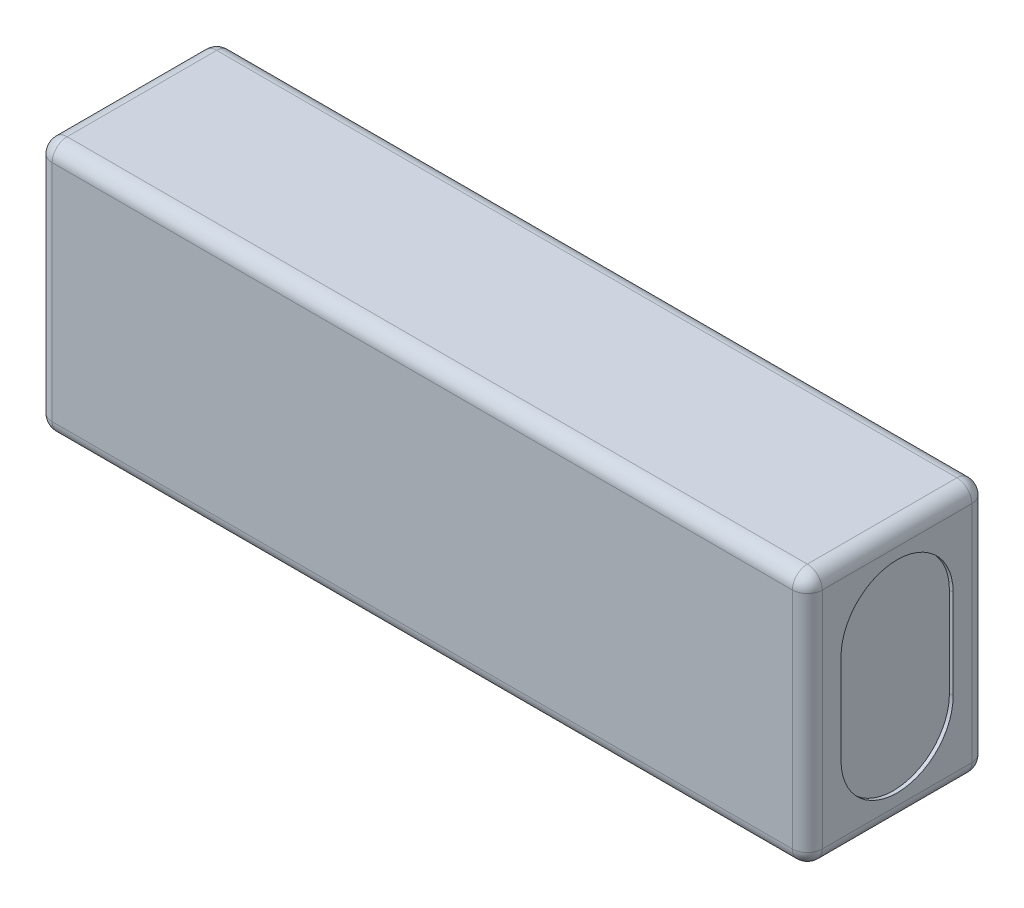
SolidWorks part; units mm, degrees
ref_plane "Plano frontal" through (0, 0, 0) normal (0, 0, 1) x (1, 0, 0)
ref_plane "Plano superior" through (0, 0, 0) normal (0, 1, 0) x (1, 0, 0)
ref_plane "Plano direito" through (0, 0, 0) normal (1, 0, 0) x (0, 0, -1)
sketch "Esboço1" plane through (0, 0, 0) normal (0, 0, 1) x (1, 0, 0)
  line L1 (-51.5, 17) -> (51.5, 17)
  line L2 (-51.5, 17) -> (-51.5, -17)
  line L3 (-51.5, -17) -> (51.5, -17)
  line L4 (51.5, 17) -> (51.5, -17)
  line L5 (-51.5, 17) -> (51.5, -17) construction
  line L6 (-51.5, -17) -> (51.5, 17) construction
  point P0 (0, 0)
  dimension "D1" = 103
  dimension "D2" = 34
extrude "Ressalto-extrusão1" add sketch "Esboço1" along normal blind 24
sketch "Esboço2" plane through (51.5, 0, 0) normal (1, 0, 0) x (0, 0, -1)
  line L0 (-12, 17) -> (-12, -17) construction
  line L1 (-24, 17) -> (0, 17) construction
  line L2 (-24, -17) -> (0, -17) construction
  line L3 (0, 0) -> (-24, 0) construction
  line L4 (-24, -17) -> (-24, 17) construction
  line L5 (-12, 6) -> (-12, -6) construction
  line L6 (-4.5, 6) -> (-4.5, -6)
  line L7 (-19.5, 6) -> (-19.5, -6)
  arc A0 (-4.5, 6) -> (-19.5, 6) centre (-12, 6) ccw
  arc A1 (-19.5, -6) -> (-4.5, -6) centre (-12, -6) ccw
  point P13 (-12, 0)
  dimension "D1" = 12
  dimension "D2" = 15
extrude "Corte-extrusão1" cut sketch "Esboço2" against normal blind 0.5
mirror "Espelhar1" about plane through (0, 0, 0) normal (1, 0, 0) of "Corte-extrusão1"
fillet "Filete1" radius 2 12 edges at (-51.5, -17, 12) (51.5, -17, 12) (-51.5, 0, 0) (0, -17, 0) (51.5, 0, 0) (51.5, 17, 12) (-51.5, 17, 12) (0, 17, 0) (0, -17, 24) (-51.5, 0, 24) (0, 17, 24) (51.5, 0, 24)
sketch "Croquis1" plane through (0, 0, 0) normal (0, 0, -1) x (-1, 0, 0)
  line L0 (13.8667, -15) -> (49.5, 3.1561) construction
  line L1 (-49.5, -15) -> (49.5, -15) construction
  line L2 (49.5, -15) -> (49.5, 15) construction
  text T0 "2200" font "Cascadia Code" height 10
  dimension "D1" = 27
extrude "Cortar-Extruir1" cut sketch "Croquis1" against normal blind 3
sketch "Croquis2" plane through (0, 0, 0) normal (0, 0, -1) x (-1, 0, 0)
  line L0 (-49.5, 3.5023) -> (-21.8627, 3.5023) construction
  line L1 (-49.5, 15) -> (-49.5, -15) construction
  line L3 (-21.8627, -1.9103) -> (-37.2514, -1.9103) construction
  text T0 "GENS ACE" font "Century Gothic" height 7
  text T1 "11.1V" font "Century Gothic" height 4
extrude "Cortar-Extruir2" cut sketch "Croquis2" against normal blind 3
